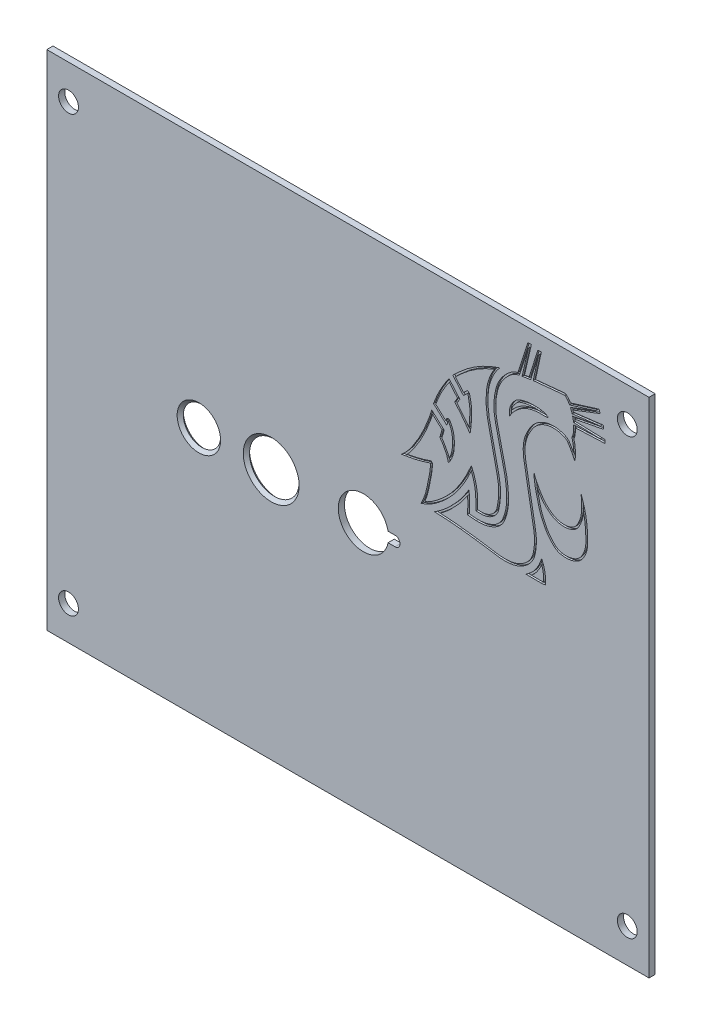
SolidWorks part; units mm, degrees
ref_plane "Front Plane" through (0, 0, 0) normal (0, 0, 1) x (1, 0, 0)
ref_plane "Top Plane" through (0, 0, 0) normal (0, 1, 0) x (1, 0, 0)
ref_plane "Right Plane" through (0, 0, 0) normal (1, 0, 0) x (0, 0, -1)
sketch "Sketch1" plane through (0, 0, 0) normal (0, 0, 1) x (1, 0, 0)
  line L1 (8, 90.5) -> (105, 90.5)
  line L2 (8, 90.5) -> (8, 9.5)
  line L3 (8, 9.5) -> (105, 9.5)
  line L4 (105, 90.5) -> (105, 9.5)
  line L7 (113.5, 99) -> (113.5, 92.5) construction
  line L8 (2, 90.5) -> (2, 9.5) construction
  line L9 (112.5, 99) -> (1, 99) construction
  line L10 (1, 1) -> (112.5, 1) construction
  dimension "D1" = 8.5
  dimension "D2" = 6
  dimension "D3" = 8.5
  dimension "D4" = 8.5
extrude "Boss-Extrude1" add sketch "Sketch1" along normal blind 1
sketch "Sketch2" plane through (0, 0, 1) normal (0, 0, 1) x (1, 0, 0)
  circle A0 centre (11.5, 15) radius 1.6
  circle A1 centre (101.5, 15) radius 1.6
  circle A2 centre (101.5, 85) radius 1.6
  circle A3 centre (11.5, 85) radius 1.6
  dimension "D1" = 3.2
extrude "Cut-Extrude1" cut sketch "Sketch2" against normal blind 1
sketch "Sketch4" plane through (0, 0, 1) normal (0, 0, 1) x (1, 0, 0)
  line L0 (8, 50) -> (122.1111, 50) construction
  line L1 (8, 90.5) -> (8, 9.5) construction
  line L2 (105, 9.5) -> (105, 90.5) construction
  line L3 (62.9702, 50.8) -> (64.1, 50.8)
  line L5 (62.9702, 49.2) -> (64.1, 49.2)
  circle A0 centre (44.15, 50) radius 4
  arc A2 (62.9702, 49.2) -> (62.9702, 50.8) centre (59, 50) cw
  arc A3 (64.1, 49.2) -> (64.1, 50.8) centre (64.1, 50) ccw
  circle A4 centre (32.5, 50) radius 3
  point P6 (84.3914, 176.5352)
  point P8 (105, 50)
  point P17 (64.1, 50)
  dimension "D1" = 8
  dimension "D3" = 8.1
  dimension "D7" = 5.1
  dimension "D5" = 0.8
  dimension "D8" = 6
  dimension "D2" = 36.15
  dimension "D4" = 0.8
  dimension "D6" = 51
  dimension "D9" = 26.5
extrude "Cut-Extrude3" cut sketch "Sketch4" against normal through all
chamfer "Chamfer1" distance 0.5 angle 45 2 edges at (35.5, 50, 1) (48.15, 50, 1)
chamfer "Chamfer2" distance 0.5 angle 45 2 edges at (35.5, 50, 0) (48.15, 50, 0)
sketch "Sketch5" plane through (0, 0, 1) normal (0, 0, 1) x (1, 0, 0)
  line L0 (268.6166, 725.3089) -> (1197.2833, 725.3089) construction
  line L1 (85.4979, 88.3797) -> (86.0543, 88.3797)
  line L2 (86.0543, 88.3797) -> (84.9477, 83.5779)
  line L3 (84.9477, 83.5779) -> (85.7043, 83.6991)
  line L4 (85.7043, 83.6991) -> (87.0962, 88.1396)
  line L5 (87.0962, 88.1396) -> (87.6562, 88.1396)
  line L6 (87.6562, 88.1396) -> (86.7275, 83.8484)
  line L7 (86.7275, 83.8484) -> (91.2975, 84.29)
  line L8 (92.3443, 83.3933) -> (96.9394, 84.813)
  line L9 (96.9394, 84.813) -> (97.1296, 84.2923)
  line L10 (97.1296, 84.2923) -> (92.7283, 82.5876)
  line L11 (92.7283, 82.5876) -> (92.824, 82.3404)
  line L12 (92.824, 82.3404) -> (97.6245, 82.9332)
  line L13 (97.6245, 82.9332) -> (97.694, 82.3705)
  line L14 (97.694, 82.3705) -> (93.052, 81.4759)
  line L15 (93.052, 81.4759) -> (93.1043, 81.2047)
  line L16 (93.1043, 81.2047) -> (97.9474, 81.0554)
  line L17 (97.9474, 81.0554) -> (97.9307, 80.5133)
  line L18 (97.9307, 80.5133) -> (93.1632, 80.3143)
  line L20 (85.2392, 71.2453) -> (86.7275, 62.8459)
  line L21 (79.9827, 56.2484) -> (77.0838, 56.6753)
  line L22 (77.0838, 56.6753) -> (74.665, 56.9664)
  line L23 (74.665, 56.9664) -> (72.9121, 57.1374)
  line L24 (72.9121, 57.1374) -> (70.4124, 57.2625)
  line L25 (76.1273, 60.8146) -> (76.0553, 59.7626)
  line L26 (76.0553, 59.7626) -> (77.2108, 59.6835)
  line L27 (81.4816, 69.3883) -> (80.2598, 74.6935)
  line L28 (83.872, 83.3933) -> (85.4979, 88.3797)
  line L29 (92.3296, 77.026) -> (91.9788, 77.6045)
  line L30 (76.0064, 63.0991) -> (75.3398, 62.0701)
  line L31 (75.3398, 62.0701) -> (74.5507, 60.993)
  line L32 (74.5507, 60.993) -> (74.0022, 60.352)
  line L33 (74.0022, 60.352) -> (73.2088, 59.519)
  line L34 (73.2088, 59.519) -> (72.8691, 59.1624)
  line L35 (72.8691, 59.1624) -> (72.3954, 58.7264)
  line L36 (72.3954, 58.7264) -> (71.8825, 58.2941)
  line L37 (71.8825, 58.2941) -> (71.3889, 57.907)
  line L38 (71.3889, 57.907) -> (70.9219, 57.578)
  line L39 (70.9219, 57.578) -> (70.4124, 57.2625)
  line L41 (91.7419, 84.1438) -> (91.9676, 83.9208)
  line L42 (91.9676, 83.9208) -> (92.0675, 83.822)
  line L43 (92.0675, 83.822) -> (92.1308, 83.7398)
  line L44 (92.1308, 83.7398) -> (92.2107, 83.6231)
  line L45 (92.2107, 83.6231) -> (92.2872, 83.4973)
  line L46 (92.2872, 83.4973) -> (92.3443, 83.3933)
  line L47 (91.6037, 84.2588) -> (91.7419, 84.1438)
  line L48 (93.1632, 80.3143) -> (93.1522, 79.954)
  line L49 (93.1522, 79.954) -> (93.1348, 79.7423)
  line L50 (93.1348, 79.7423) -> (93.1127, 79.4991)
  line L51 (93.1127, 79.4991) -> (93.0955, 79.3506)
  line L52 (93.0955, 79.3506) -> (93.0744, 79.2184)
  line L53 (93.0744, 79.2184) -> (93.052, 79.0963)
  line L54 (93.052, 79.0963) -> (93.0243, 78.997)
  line L55 (93.0243, 78.997) -> (92.9796, 78.8581)
  line L56 (92.9796, 78.8581) -> (92.9441, 78.7632)
  line L57 (92.9441, 78.7632) -> (92.9032, 78.684)
  line L58 (92.3296, 77.026) -> (92.7101, 76.3369)
  line L59 (92.7101, 76.3369) -> (93.052, 75.6446)
  line L60 (93.052, 75.6446) -> (93.0995, 75.9669)
  line L61 (93.0995, 75.9669) -> (93.1341, 76.202)
  line L62 (93.1341, 76.202) -> (93.143, 76.5101)
  line L63 (93.143, 76.5101) -> (93.143, 76.6814)
  line L64 (93.143, 76.6814) -> (93.1376, 76.8449)
  line L65 (93.1376, 76.8449) -> (93.1258, 77.2029)
  line L66 (93.1258, 77.2029) -> (93.1093, 77.499)
  line L67 (93.1093, 77.499) -> (93.0841, 77.8429)
  line L68 (93.0841, 77.8429) -> (93.0789, 77.8817)
  line L69 (93.0789, 77.8817) -> (93.0712, 77.9224)
  line L70 (93.0712, 77.9224) -> (93.0621, 77.9573)
  line L71 (93.0621, 77.9573) -> (93.0438, 78.0267)
  line L72 (93.0438, 78.0267) -> (92.9796, 78.3132)
  line L73 (92.9796, 78.3132) -> (92.9032, 78.6542)
  line L74 (92.9032, 78.6542) -> (92.9032, 78.684)
  line L75 (82.5296, 76.6184) -> (82.5296, 77.3228)
  line L76 (84.3989, 79.7986) -> (84.7639, 79.8997)
  line L77 (86.5207, 80.1144) -> (86.8937, 80.1144)
  line L78 (88.7012, 79.6134) -> (88.7012, 79.5841)
  line L79 (88.4081, 79.4748) -> (87.3705, 79.4748)
  line L80 (86.439, 70.8945) -> (86.553, 70.4925)
  line L81 (94.0402, 71.5878) -> (94.2371, 71.0412)
  line L82 (88.3208, 63.7824) -> (87.7958, 64.8727)
  line L83 (87.211, 66.5734) -> (86.8262, 68.1425)
  line L84 (87.697, 59.3718) -> (87.5655, 58.9816)
  line L85 (85.1462, 55.919) -> (87.6158, 55.9059)
  line L86 (88.3208, 55.9797) -> (88.3341, 56.4474)
  line L87 (75.7914, 76.4372) -> (75.1163, 75.7925)
  line L88 (75.1163, 75.7925) -> (73.3922, 77.7882)
  line L89 (73.3922, 77.7882) -> (74.5507, 78.8581)
  line L90 (80.9649, 82.5876) -> (80.7218, 82.2861)
  line L91 (80.7218, 82.2861) -> (80.5258, 82.0431)
  line L92 (80.5258, 82.0431) -> (80.3277, 81.7417)
  line L93 (79.093, 77.9224) -> (79.0618, 76.5504)
  line L94 (79.0774, 76.2897) -> (79.2686, 74.6935)
  line L95 (79.2686, 74.6935) -> (79.563, 73.3465)
  line L96 (79.563, 73.3465) -> (80.8369, 67.5165)
  line L97 (78.0165, 60.7111) -> (77.1048, 60.7111)
  line L98 (77.1048, 60.7111) -> (77.1048, 62.2526)
  line L99 (76.3787, 65.9226) -> (75.7914, 64.6822)
  line L100 (75.7914, 64.6822) -> (75.3398, 63.8618)
  line L101 (75.3398, 63.8618) -> (74.9353, 63.1864)
  line L102 (75.8238, 76.3821) -> (75.9265, 75.9123)
  line L103 (75.9265, 75.9123) -> (76.0553, 75.1902)
  line L104 (75.9909, 71.7883) -> (75.5414, 72.433)
  line L105 (75.5414, 72.433) -> (74.9353, 73.2111)
  line L106 (74.9353, 73.2111) -> (74.5957, 73.6224)
  line L107 (74.5957, 73.6224) -> (74.3733, 73.8632)
  line L108 (74.3733, 73.8632) -> (74.0607, 74.2252)
  line L109 (74.0607, 74.2252) -> (74.5242, 74.9986)
  line L110 (74.5242, 74.9986) -> (72.8019, 76.9923)
  line L111 (72.8019, 76.9923) -> (72.4237, 76.466)
  line L112 (72.4237, 76.466) -> (72.2115, 76.1707)
  line L113 (72.2115, 76.1707) -> (71.4816, 74.9308)
  line L114 (71.4816, 74.9308) -> (71.357, 74.7027)
  line L115 (71.357, 74.7027) -> (71.2592, 74.5105)
  line L116 (70.2958, 72.2629) -> (72.4237, 70.334)
  line L117 (72.4237, 70.334) -> (72.6753, 71.0412)
  line L118 (72.7379, 70.9746) -> (72.8691, 70.6876)
  line L119 (72.8691, 70.6876) -> (72.9584, 70.4925)
  line L120 (73.3327, 68.7739) -> (73.3327, 67.9785)
  line L121 (72.8035, 65.9226) -> (72.7379, 66.1445)
  line L122 (72.5495, 66.5734) -> (72.2555, 67.1441)
  line L123 (71.6355, 68.1425) -> (72.0093, 69.4205)
  line L124 (72.0093, 69.4205) -> (70.0008, 71.2242)
  line L125 (70.0008, 71.2242) -> (69.7755, 70.5058)
  line L126 (69.5813, 69.9598) -> (69.5299, 69.8151)
  line L127 (65.1696, 62.6382) -> (65.7984, 62.734)
  line L128 (69.8337, 63.6119) -> (69.6836, 62.326)
  line L129 (69.6836, 62.326) -> (69.2492, 60.126)
  line L130 (85.585, 87.6794) -> (85.585, 87.6794)
  line L131 (85.585, 87.6794) -> (84.5554, 83.2111)
  line L132 (84.5554, 83.2111) -> (85.935, 83.4323)
  line L133 (85.935, 83.4323) -> (87.2126, 87.5081)
  line L134 (87.2126, 87.5081) -> (87.2126, 87.5081)
  line L135 (87.2126, 87.5081) -> (86.3474, 83.5103)
  line L136 (86.3474, 83.5103) -> (91.3264, 83.9914)
  line L137 (91.4511, 83.9955) -> (91.5402, 83.9214)
  line L138 (91.5402, 83.9214) -> (91.7566, 83.7074)
  line L139 (91.7566, 83.7074) -> (91.8422, 83.6229)
  line L140 (91.8422, 83.6229) -> (91.888, 83.5634)
  line L141 (91.888, 83.5634) -> (91.9586, 83.4602)
  line L142 (91.9586, 83.4602) -> (92.0274, 83.3471)
  line L143 (92.0274, 83.3471) -> (92.199, 83.0345)
  line L144 (92.199, 83.0345) -> (96.4127, 84.3363)
  line L145 (96.4127, 84.3363) -> (96.4127, 84.3363)
  line L146 (96.4127, 84.3363) -> (92.3402, 82.759)
  line L147 (92.3402, 82.759) -> (92.6287, 82.014)
  line L148 (92.6287, 82.014) -> (97.1654, 82.5742)
  line L149 (97.1654, 82.5742) -> (97.1654, 82.5742)
  line L150 (97.1654, 82.5742) -> (92.7007, 81.7137)
  line L151 (92.7007, 81.7137) -> (92.8551, 80.9123)
  line L152 (92.8551, 80.9123) -> (97.1353, 80.7803)
  line L153 (97.1353, 80.7803) -> (97.1353, 80.7803)
  line L154 (97.1353, 80.7803) -> (92.8719, 80.6024)
  line L155 (92.8719, 80.6024) -> (92.8526, 79.9708)
  line L156 (92.8526, 79.9708) -> (92.8359, 79.7682)
  line L157 (92.8359, 79.7682) -> (92.8143, 79.53)
  line L158 (92.8143, 79.53) -> (92.7982, 79.3915)
  line L159 (92.7982, 79.3915) -> (92.7787, 79.2691)
  line L160 (92.7787, 79.2691) -> (92.7594, 79.1638)
  line L161 (92.7594, 79.1638) -> (92.737, 79.0833)
  line L162 (92.737, 79.0833) -> (92.6962, 78.9567)
  line L163 (92.6962, 78.9567) -> (92.6694, 78.885)
  line L164 (92.6694, 78.885) -> (92.6032, 78.7569)
  line L165 (92.6032, 78.621) -> (92.6032, 78.7569)
  line L166 (92.6869, 78.2477) -> (92.6032, 78.621)
  line L167 (92.7523, 77.9557) -> (92.6869, 78.2477)
  line L168 (92.7719, 77.8809) -> (92.7523, 77.9557)
  line L169 (92.7784, 77.8563) -> (92.7719, 77.8809)
  line L170 (92.7826, 77.834) -> (92.7784, 77.8563)
  line L171 (92.7856, 77.8121) -> (92.7826, 77.834)
  line L172 (92.8099, 77.4797) -> (92.7856, 77.8121)
  line L173 (92.8261, 77.1897) -> (92.8099, 77.4797)
  line L174 (92.8378, 76.8351) -> (92.8261, 77.1897)
  line L175 (92.8416, 76.7194) -> (92.8378, 76.8351)
  line L176 (92.8416, 76.7194) -> (92.8416, 76.7194)
  line L177 (92.8416, 76.7194) -> (92.8416, 76.7194)
  line L178 (92.8416, 76.7194) -> (92.8416, 76.7194)
  line L179 (92.8416, 76.7194) -> (92.8416, 76.7194)
  line L180 (92.8416, 76.7194) -> (92.8416, 76.7194)
  line L181 (92.5893, 77.1763) -> (92.8416, 76.7194)
  line L182 (92.5893, 77.1763) -> (92.2354, 77.76)
  line L183 (84.9446, 71.1881) -> (86.4321, 62.7935)
  line L184 (80.034, 56.544) -> (77.1235, 56.9726)
  line L185 (77.1235, 56.9726) -> (74.6974, 57.2646)
  line L186 (74.6974, 57.2646) -> (72.9342, 57.4366)
  line L187 (72.9342, 57.4366) -> (71.3544, 57.5157)
  line L188 (71.3544, 57.5157) -> (71.3544, 57.5157)
  line L189 (71.568, 57.6662) -> (71.3544, 57.5157)
  line L190 (72.0718, 58.0613) -> (71.568, 57.6662)
  line L191 (72.5937, 58.5012) -> (72.0718, 58.0613)
  line L192 (73.0796, 58.9484) -> (72.5937, 58.5012)
  line L193 (73.426, 59.3121) -> (73.0796, 58.9484)
  line L194 (74.2249, 60.1509) -> (73.426, 59.3121)
  line L195 (74.786, 60.8066) -> (74.2249, 60.1509)
  line L196 (75.5869, 61.8998) -> (74.786, 60.8066)
  line L197 (75.7756, 62.1911) -> (75.5869, 61.8998)
  line L198 (75.8272, 60.8229) -> (75.7355, 59.4838)
  line L199 (75.7355, 59.4838) -> (77.1903, 59.3842)
  line L200 (81.7728, 69.4608) -> (80.5522, 74.7608)
  line L201 (84.106, 83.1435) -> (85.585, 87.6794)
  line L202 (82.8543, 77.6318) -> (82.8543, 77.6318)
  line L203 (84.4757, 79.5086) -> (84.844, 79.6106)
  line L204 (86.5166, 79.8144) -> (86.8937, 79.8144)
  line L205 (87.4345, 79.7748) -> (87.4345, 79.7748)
  line L206 (87.4345, 79.7748) -> (87.3705, 79.7748)
  line L207 (86.9626, 68.9287) -> (86.9626, 68.9287)
  line L208 (94.4512, 69.2278) -> (94.4512, 69.2278)
  line L209 (88.5874, 63.9204) -> (88.066, 65.0029)
  line L210 (87.5034, 66.6409) -> (87.1175, 68.214)
  line L211 (87.7198, 58.5347) -> (87.7198, 58.5347)
  line L212 (86.0711, 56.2141) -> (87.6174, 56.2059)
  line L213 (88.0279, 56.2325) -> (88.0342, 56.4559)
  line L214 (75.7158, 76.7797) -> (75.1372, 76.2272)
  line L215 (75.1372, 76.2272) -> (73.8089, 77.7647)
  line L216 (73.8089, 77.7647) -> (74.7542, 78.6377)
  line L217 (80.1214, 81.9741) -> (80.1214, 81.9741)
  line L218 (80.1214, 81.9741) -> (80.1214, 81.9741)
  line L219 (80.1214, 81.9741) -> (80.077, 81.9066)
  line L220 (78.7932, 77.9324) -> (78.7619, 76.5572)
  line L221 (78.7799, 76.2507) -> (78.9725, 74.6435)
  line L222 (78.9725, 74.6435) -> (79.2699, 73.2825)
  line L223 (79.2699, 73.2825) -> (80.5438, 67.4524)
  line L224 (78.0165, 61.0111) -> (77.4048, 61.0111)
  line L225 (77.4048, 61.0111) -> (77.4048, 62.2526)
  line L226 (76.3852, 66.6373) -> (75.5242, 64.8189)
  line L227 (75.5242, 64.8189) -> (75.0796, 64.0113)
  line L228 (75.0796, 64.0113) -> (74.6779, 63.3405)
  line L229 (69.9802, 62.2795) -> (69.5435, 60.0679)
  line L230 (70.1334, 63.5919) -> (69.9802, 62.2795)
  line L231 (66.0527, 63.0783) -> (66.0527, 63.0783)
  line L232 (69.8621, 69.8541) -> (69.8126, 69.7147)
  line L233 (70.1475, 70.6893) -> (70.0618, 70.4161)
  line L234 (71.6683, 69.3235) -> (70.1475, 70.6893)
  line L235 (71.3053, 68.0821) -> (71.6683, 69.3235)
  line L236 (72.2874, 66.4271) -> (71.9888, 67.0067)
  line L237 (72.6998, 65.2154) -> (72.4502, 66.0594)
  line L238 (73.6327, 68.7739) -> (73.6327, 67.9785)
  line L239 (73.142, 70.8124) -> (73.2312, 70.6172)
  line L240 (73.0169, 71.0859) -> (73.142, 70.8124)
  line L241 (72.2919, 70.8585) -> (72.4478, 71.2968)
  line L242 (70.646, 72.3504) -> (72.2919, 70.8585)
  line L243 (71.6224, 74.5627) -> (71.5266, 74.3745)
  line L244 (71.7425, 74.7827) -> (71.6224, 74.5627)
  line L245 (72.4631, 76.0067) -> (71.7425, 74.7827)
  line L246 (72.6674, 76.291) -> (72.4631, 76.0067)
  line L247 (72.8235, 76.5083) -> (72.6674, 76.291)
  line L248 (74.1553, 74.9667) -> (72.8235, 76.5083)
  line L249 (73.6918, 74.1933) -> (74.1553, 74.9667)
  line L250 (74.1496, 73.6634) -> (73.6918, 74.1933)
  line L251 (74.3697, 73.425) -> (74.1496, 73.6634)
  line L252 (74.7013, 73.0234) -> (74.3697, 73.425)
  line L253 (75.2999, 72.255) -> (74.7013, 73.0234)
  line L254 (76.1789, 70.994) -> (75.2999, 72.255)
  line L255 (76.2208, 75.9707) -> (76.3506, 75.2429)
  line L256 (76.1149, 76.4554) -> (76.2208, 75.9707)
  arc A7 (76.0064, 63.0991) -> (76.1273, 60.8146) centre (47.2271, 60.4302) cw
  arc A8 (77.2108, 59.6835) -> (80.1009, 60.3115) centre (77.5732, 64.9798) ccw
  arc A9 (80.1009, 60.3115) -> (81.4816, 61.8493) centre (78.6375, 63.0142) ccw
  arc A10 (81.4816, 61.8493) -> (82.0768, 64.8727) centre (74.1002, 64.8727) ccw
  arc A11 (82.0768, 64.8727) -> (81.4816, 69.3883) centre (64.6509, 64.8727) ccw
  arc A12 (80.2598, 74.6935) -> (80.3277, 79.3371) centre (89.7421, 76.8773) cw
  arc A13 (80.3277, 79.3371) -> (82.6203, 82.7718) centre (86.439, 77.7403) cw
  arc A14 (82.6203, 82.7718) -> (83.872, 83.3933) centre (84.8768, 79.7986) cw
  arc A15 (91.9788, 77.6045) -> (91.401, 78.1208) centre (90.8448, 76.9168) ccw
  arc A16 (91.401, 78.1208) -> (89.4144, 78.5072) centre (89.6204, 74.2662) ccw
  arc A17 (89.4144, 78.5072) -> (86.2381, 76.7255) centre (89.6124, 74.4321) ccw
  arc A18 (86.2381, 76.7255) -> (85.4979, 75.3955) centre (93.3129, 71.9168) ccw
  arc A19 (85.4979, 75.3955) -> (85.0337, 73.2111) centre (90.4053, 73.2111) ccw
  arc A20 (85.0337, 73.2111) -> (85.2392, 71.2453) centre (94.5391, 73.2111) ccw
  arc A21 (86.7275, 62.8459) -> (86.6527, 59.4071) centre (78.0814, 61.3138) cw
  arc A22 (86.6527, 59.4071) -> (85.6157, 57.5353) centre (82.9634, 60.2278) cw
  arc A23 (85.6157, 57.5353) -> (82.6203, 56.1239) centre (82.1071, 61.097) cw
  arc A24 (82.6203, 56.1239) -> (79.9827, 56.2484) centre (81.7134, 64.9126) cw
  arc A25 (91.2975, 84.29) -> (91.5183, 84.2923) centre (91.4209, 83.0131) cw
  arc A26 (91.5183, 84.2923) -> (91.6037, 84.2588) centre (91.5064, 84.1361) cw
  arc A27 (82.5296, 77.3228) -> (82.8185, 78.4246) centre (84.7742, 77.3228) cw
  arc A28 (82.8185, 78.4246) -> (83.4778, 79.2825) centre (86.1454, 76.5504) cw
  arc A29 (83.4778, 79.2825) -> (84.3989, 79.7986) centre (84.8981, 77.8279) cw
  arc A30 (84.7639, 79.8997) -> (86.5207, 80.1144) centre (86.3597, 74.1366) cw
  arc A31 (86.8937, 80.1144) -> (88.0164, 79.954) centre (86.8937, 76.1056) cw
  arc A32 (88.0164, 79.954) -> (88.6016, 79.717) centre (87.1397, 76.9488) cw
  arc A33 (88.6016, 79.717) -> (88.7012, 79.6134) centre (88.4945, 79.5142) cw
  arc A34 (88.7012, 79.5841) -> (88.6328, 79.4991) centre (88.6142, 79.5841) cw
  arc A35 (88.6328, 79.4991) -> (88.4081, 79.4748) centre (88.4081, 80.5249) cw
  arc A36 (87.3705, 79.4748) -> (82.5296, 76.6184) centre (87.3705, 73.9443) ccw
  arc A37 (86.553, 70.4925) -> (86.6859, 70.137) centre (88.797, 71.1288) ccw
  arc A38 (86.6859, 70.137) -> (87.6562, 68.3236) centre (104.5436, 78.5266) ccw
  arc A39 (87.6562, 68.3236) -> (89.4585, 66.4598) centre (92.6271, 71.3269) ccw
  arc A40 (89.4585, 66.4598) -> (92.2872, 66.0522) centre (91.3125, 69.3077) ccw
  arc A41 (92.2872, 66.0522) -> (93.4389, 66.951) centre (91.7105, 67.9785) ccw
  arc A42 (93.4389, 66.951) -> (94.1622, 69.4945) centre (89.0066, 69.5859) ccw
  arc A43 (94.1622, 69.4945) -> (94.0402, 71.5878) centre (80.3413, 69.7395) ccw
  arc A44 (94.2371, 71.0412) -> (95.0063, 67.6873) centre (80.7554, 66.1843) cw
  arc A45 (95.0063, 67.6873) -> (95.1259, 65.1241) centre (73.1613, 65.3835) cw
  arc A46 (95.1259, 65.1241) -> (94.367, 62.7199) centre (90.7748, 65.1755) cw
  arc A47 (94.367, 62.7199) -> (92.9476, 61.6318) centre (92.0001, 64.3379) cw
  arc A48 (92.9476, 61.6318) -> (90.7748, 61.5059) centre (91.6414, 65.3625) cw
  arc A49 (90.7748, 61.5059) -> (89.7734, 62.0061) centre (91.2863, 63.7824) cw
  arc A50 (89.7734, 62.0061) -> (88.3208, 63.7824) centre (93.9326, 66.8894) cw
  arc A51 (87.7958, 64.8727) -> (87.211, 66.5734) centre (94.6956, 68.1958) cw
  arc A52 (86.8262, 68.1425) -> (86.439, 70.8945) centre (100.2412, 71.4331) cw
  arc A53 (87.5655, 58.9816) -> (86.6527, 57.2625) centre (81.8914, 60.8929) cw
  arc A54 (86.6527, 57.2625) -> (85.1462, 55.919) centre (82.4263, 60.485) cw
  arc A55 (87.6158, 55.9059) -> (88.3208, 55.9797) centre (87.633, 59.1444) ccw
  arc A56 (88.3341, 56.4474) -> (87.697, 59.3718) centre (82.1107, 56.6233) ccw
  arc A57 (74.5507, 78.8581) -> (80.9649, 82.5876) centre (86.1367, 66.3122) cw
  arc A58 (80.3277, 81.7417) -> (79.093, 77.9224) centre (86.6397, 77.5921) ccw
  arc A59 (79.0618, 76.5504) -> (79.0774, 76.2897) centre (80.643, 76.5144) ccw
  arc A60 (80.8369, 67.5165) -> (80.799, 62.7199) centre (70.2442, 65.2018) cw
  arc A61 (80.799, 62.7199) -> (80.4267, 61.9055) centre (78.5814, 63.2413) cw
  arc A62 (80.4267, 61.9055) -> (79.4158, 61.0408) centre (78.1283, 63.5694) cw
  arc A63 (79.4158, 61.0408) -> (78.6375, 60.7718) centre (78.0589, 63.7056) cw
  arc A64 (78.6375, 60.7718) -> (78.0165, 60.7111) centre (78.0165, 63.9209) cw
  arc A65 (77.1048, 62.2526) -> (76.3787, 65.9226) centre (67.4671, 62.2526) ccw
  arc A66 (74.9353, 63.1864) -> (72.4645, 60.0789) centre (62.0135, 70.9244) cw
  arc A67 (72.4645, 60.0789) -> (70.4124, 58.3876) centre (60.5598, 72.433) cw
  arc A68 (70.4124, 58.3876) -> (68.3095, 57.376) centre (66.292, 64.2614) cw
  arc A69 (75.7914, 76.4372) -> (75.8238, 76.3821) centre (75.6902, 76.3405) cw
  arc A70 (76.0553, 75.1902) -> (76.1419, 74.2111) centre (70.5667, 74.2111) cw
  arc A71 (76.1419, 74.2111) -> (75.9909, 71.7883) centre (56.6354, 74.2111) cw
  arc A72 (71.2592, 74.5105) -> (70.2958, 72.2629) centre (87.8048, 66.0885) ccw
  arc A73 (72.6753, 71.0412) -> (72.7379, 70.9746) centre (72.6417, 70.9469) cw
  arc A74 (72.9584, 70.4925) -> (73.3327, 68.7739) centre (69.2002, 68.7739) cw
  arc A75 (73.3327, 67.9785) -> (72.8035, 65.9226) centre (69.0741, 67.9785) cw
  arc A76 (72.7379, 66.1445) -> (72.5495, 66.5734) centre (70.9546, 65.6172) ccw
  arc A77 (72.2555, 67.1441) -> (71.6355, 68.1425) centre (65.722, 63.7786) ccw
  arc A78 (69.7755, 70.5058) -> (69.5813, 69.9598) centre (62.4753, 72.7953) cw
  arc A79 (69.5299, 69.8151) -> (66.8697, 64.5729) centre (47.8831, 77.5038) cw
  arc A80 (66.8697, 64.5729) -> (65.1696, 62.6382) centre (58.1964, 70.4799) cw
  arc A81 (65.7984, 62.734) -> (69.8135, 63.7314) centre (62.4131, 84.9422) ccw
  arc A82 (69.8135, 63.7314) -> (69.8337, 63.6119) centre (69.4711, 63.6119) cw
  arc A83 (69.2492, 60.126) -> (68.3095, 57.376) centre (58.6053, 62.2276) cw
  arc A84 (91.3264, 83.9914) -> (91.4511, 83.9955) centre (91.4209, 83.0131) cw
  arc A85 (91.4511, 83.9955) -> (91.4511, 83.9955) centre (91.4511, 83.9955) cw
  arc A86 (92.2354, 77.76) -> (91.5268, 78.3931) centre (90.8448, 76.9168) ccw
  arc A87 (91.5268, 78.3931) -> (89.3998, 78.8068) centre (89.6204, 74.2662) ccw
  arc A88 (89.3998, 78.8068) -> (85.99, 76.8941) centre (89.6124, 74.4321) ccw
  arc A89 (85.99, 76.8941) -> (85.2238, 75.5175) centre (93.3129, 71.9168) ccw
  arc A90 (85.2238, 75.5175) -> (84.7337, 73.2111) centre (90.4053, 73.2111) ccw
  arc A91 (84.7337, 73.2111) -> (84.9446, 71.1881) centre (94.5391, 73.2111) ccw
  arc A92 (86.4321, 62.7935) -> (86.3598, 59.4723) centre (78.0814, 61.3138) cw
  arc A93 (86.3598, 59.4723) -> (85.4052, 57.749) centre (82.9634, 60.2278) cw
  arc A94 (85.4052, 57.749) -> (82.5895, 56.4223) centre (82.1071, 61.097) cw
  arc A95 (82.5895, 56.4223) -> (80.034, 56.544) centre (81.7134, 64.9126) cw
  arc A96 (75.7756, 62.1911) -> (75.8272, 60.8229) centre (47.2271, 60.4302) cw
  arc A97 (77.1903, 59.3842) -> (80.2437, 60.0477) centre (77.5732, 64.9798) ccw
  arc A98 (80.2437, 60.0477) -> (81.7592, 61.7356) centre (78.6375, 63.0142) ccw
  arc A99 (81.7592, 61.7356) -> (82.3768, 64.8727) centre (74.1002, 64.8727) ccw
  arc A100 (82.3768, 64.8727) -> (81.7728, 69.4608) centre (64.6509, 64.8727) ccw
  arc A101 (80.5522, 74.7608) -> (80.6179, 79.2613) centre (89.7421, 76.8773) cw
  arc A102 (80.6179, 79.2613) -> (82.8017, 82.5329) centre (86.439, 77.7403) cw
  arc A103 (82.8017, 82.5329) -> (84.106, 83.1435) centre (84.8768, 79.7986) cw
  arc A104 (82.8543, 77.6318) -> (83.0799, 78.2773) centre (84.7742, 77.3228) cw
  arc A105 (83.0799, 78.2773) -> (83.6874, 79.0678) centre (86.1454, 76.5504) cw
  arc A106 (83.6874, 79.0678) -> (84.4757, 79.5086) centre (84.8981, 77.8279) cw
  arc A107 (84.844, 79.6106) -> (86.5166, 79.8144) centre (86.3597, 74.1366) cw
  arc A108 (86.8937, 79.8144) -> (87.4345, 79.7748) centre (86.8937, 76.1056) cw
  arc A109 (87.4345, 79.7748) -> (87.4345, 79.7748) centre (87.4345, 79.7748) ccw
  arc A110 (87.4345, 79.7748) -> (87.4345, 79.7748) centre (87.4345, 79.7748) ccw
  arc A111 (87.4345, 79.7748) -> (87.4345, 79.7748) centre (87.4345, 79.7748) ccw
  arc A112 (87.4345, 79.7748) -> (87.4345, 79.7748) centre (87.4345, 79.7748) ccw
  arc A113 (87.3705, 79.7748) -> (82.8543, 77.6318) centre (87.3705, 73.9443) ccw
  arc A114 (86.9626, 68.9287) -> (86.9626, 68.9287) centre (86.9626, 68.9287) ccw
  arc A115 (86.9626, 68.9287) -> (87.3995, 68.1685) centre (104.5436, 78.5266) ccw
  arc A116 (87.3995, 68.1685) -> (89.2948, 66.2083) centre (92.6271, 71.3269) ccw
  arc A117 (89.2948, 66.2083) -> (92.3733, 65.7648) centre (91.3125, 69.3077) ccw
  arc A118 (92.3733, 65.7648) -> (93.6968, 66.7977) centre (91.7105, 67.9785) ccw
  arc A119 (93.6968, 66.7977) -> (94.4512, 69.2278) centre (89.0066, 69.5859) ccw
  arc A120 (94.4512, 69.2278) -> (94.4512, 69.2278) centre (94.4512, 69.2278) cw
  arc A121 (94.4512, 69.2278) -> (94.7079, 67.6558) centre (80.7554, 66.1843) cw
  arc A122 (94.7079, 67.6558) -> (94.8259, 65.1277) centre (73.1613, 65.3835) cw
  arc A123 (94.8259, 65.1277) -> (94.1194, 62.8892) centre (90.7748, 65.1755) cw
  arc A124 (94.1194, 62.8892) -> (92.8485, 61.915) centre (92.0001, 64.3379) cw
  arc A125 (92.8485, 61.915) -> (90.8406, 61.7986) centre (91.6414, 65.3625) cw
  arc A126 (90.8406, 61.7986) -> (89.9679, 62.2345) centre (91.2863, 63.7824) cw
  arc A127 (89.9679, 62.2345) -> (88.5874, 63.9204) centre (93.9326, 66.8894) cw
  arc A128 (88.066, 65.0029) -> (87.5034, 66.6409) centre (94.6956, 68.1958) cw
  arc A129 (87.1175, 68.214) -> (86.9626, 68.9287) centre (100.2412, 71.4331) cw
  arc A130 (87.7198, 58.5347) -> (86.8912, 57.0806) centre (81.8914, 60.8929) cw
  arc A131 (86.8912, 57.0806) -> (86.0711, 56.2141) centre (82.4263, 60.485) cw
  arc A132 (87.6174, 56.2059) -> (88.0279, 56.2325) centre (87.633, 59.1444) ccw
  arc A133 (88.0342, 56.4559) -> (87.7198, 58.5347) centre (82.1107, 56.6233) ccw
  arc A134 (74.7542, 78.6377) -> (80.1214, 81.9741) centre (86.1367, 66.3122) cw
  arc A135 (80.077, 81.9066) -> (78.7932, 77.9324) centre (86.6397, 77.5921) ccw
  arc A136 (78.7619, 76.5572) -> (78.7799, 76.2507) centre (80.643, 76.5144) ccw
  arc A137 (80.5438, 67.4524) -> (80.5069, 62.7885) centre (70.2442, 65.2018) cw
  arc A138 (80.5069, 62.7885) -> (80.1837, 62.0814) centre (78.5814, 63.2413) cw
  arc A139 (80.1837, 62.0814) -> (79.2797, 61.3082) centre (78.1283, 63.5694) cw
  arc A140 (79.2797, 61.3082) -> (78.5794, 61.0661) centre (78.0589, 63.7056) cw
  arc A141 (78.5794, 61.0661) -> (78.0165, 61.0111) centre (78.0165, 63.9209) cw
  arc A142 (77.4048, 62.2526) -> (76.3852, 66.6373) centre (67.4671, 62.2526) ccw
  arc A143 (74.6779, 63.3405) -> (72.2564, 60.2949) centre (62.0135, 70.9244) cw
  arc A144 (72.2564, 60.2949) -> (70.2401, 58.6332) centre (60.5598, 72.433) cw
  arc A145 (70.2401, 58.6332) -> (68.8767, 57.8909) centre (66.292, 64.2614) cw
  arc A146 (69.5435, 60.0679) -> (68.8767, 57.8909) centre (58.6053, 62.2276) cw
  arc A147 (69.9292, 64.0907) -> (70.1334, 63.5919) centre (69.4711, 63.6119) cw
  arc A148 (66.0527, 63.0783) -> (69.9292, 64.0907) centre (62.4131, 84.9422) ccw
  arc A149 (67.1177, 64.4041) -> (66.0527, 63.0783) centre (58.1964, 70.4799) cw
  arc A150 (69.8126, 69.7147) -> (67.1177, 64.4041) centre (47.8831, 77.5038) cw
  arc A151 (70.0618, 70.4161) -> (69.8621, 69.8541) centre (62.4753, 72.7953) cw
  arc A152 (71.9888, 67.0067) -> (71.3053, 68.0821) centre (65.722, 63.7786) ccw
  arc A153 (72.4502, 66.0594) -> (72.2874, 66.4271) centre (70.9546, 65.6172) ccw
  arc A154 (73.6327, 67.9785) -> (72.6998, 65.2154) centre (69.0741, 67.9785) cw
  arc A155 (73.2312, 70.6172) -> (73.6327, 68.7739) centre (69.2002, 68.7739) cw
  arc A156 (72.4478, 71.2968) -> (73.0169, 71.0859) centre (72.6417, 70.9469) cw
  arc A157 (71.5266, 74.3745) -> (70.646, 72.3504) centre (87.8048, 66.0885) ccw
  arc A158 (76.4419, 74.2111) -> (76.1789, 70.994) centre (56.6354, 74.2111) cw
  arc A159 (76.3506, 75.2429) -> (76.4419, 74.2111) centre (70.5667, 74.2111) cw
  arc A160 (75.7158, 76.7797) -> (76.1149, 76.4554) centre (75.6902, 76.3405) cw
  dimension "D1" = 0.3
extrude "Cut-Extrude4" cut sketch "Sketch5" against normal blind 0.3 contours A26 A25 L7 L6 L5 L4 L3 L2 L1 L28 A14 A13 A12 L27 A11 A10 A9 A8 L26 L25 A7 L30 L31 L32 L33 L34 L35 L36 L37 L38 L39 L24 L23 L22 L21 A24 A23 A22 A21 L20 A20 A19 A18 A17 A16 A15 L29 L58 L59 L60 L61 | L129 A83 A68 A67 A66 L101 L100 L99 A65 L98 L97 A64 A63 A62 A61 A60 L96 L95 L94 A59 L93 A58 L92 L91 L90 A57 L89 L88 L87 A69 L102 L103 A70 A71 L104 L105 L106 L107 L108 L109 L110 L111 L112 L113 L114 L115 A72 L116 L117 A73 L118 | L86 A56 L84 A53 A54 L85 A55 A133 L213 A132 L212 A131 A130 L211 | A52 L83 A51 L82 A50 A49 A48 A47 A46 A45 A44 L81 A43 A42 A41 A40 A39 A38 A37 L80 L210 A129 A114 A115 A116 A117 A118 A119 A120 A121 A122 A123 A124 A125 A126 A127 L209 A128 | A36 L79 A35 A34 L78 A33 A32 A31 L77 A30 L76 A29 A28 A27 L75 L206 A113 L202 A104 A105 A106 L203 A107 L204 A108 A109 A110 A112 region at (85.7761, 87.9553, 1) region at (85.125, 79.0997, 1) region at (86.4831, 70.6898, 1) region at (88.1479, 57.9385, 1) region at (75.2479, 76.3305, 1)
